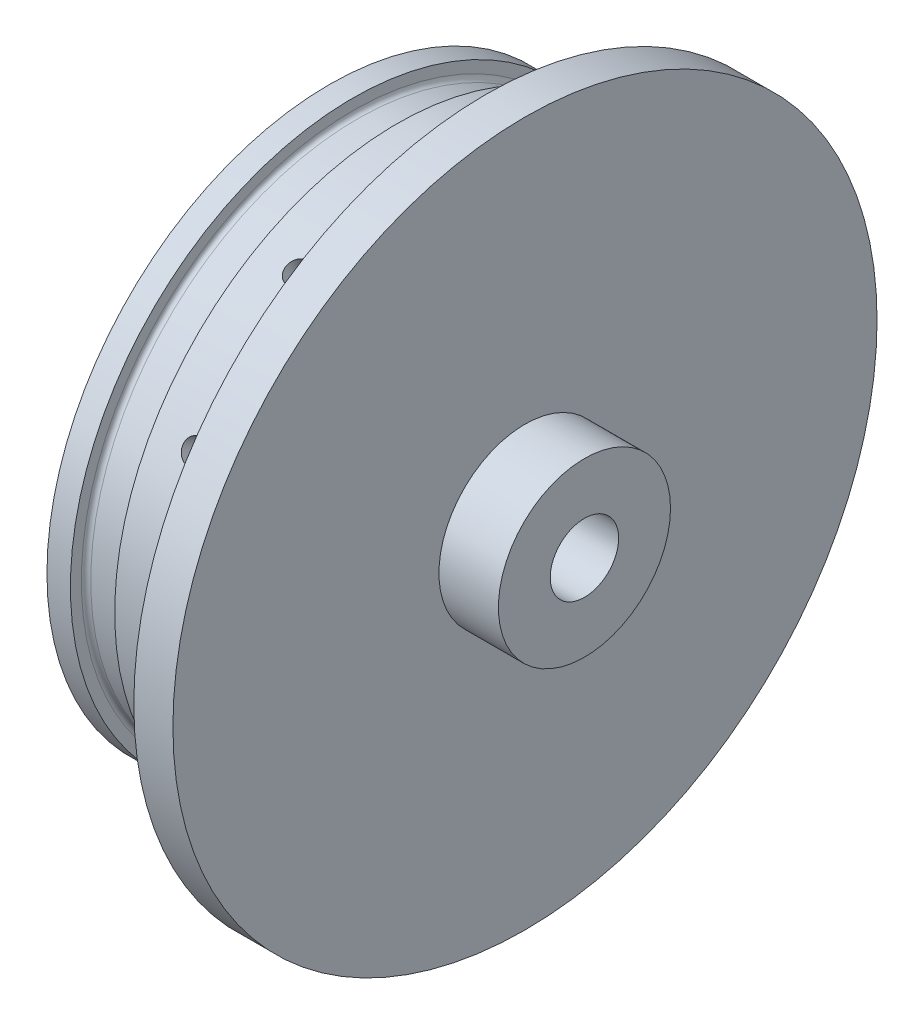
SolidWorks part; units mm, degrees
material "7075-T6 (SN)"
ref_plane "Front Plane" through (0, 0, 0) normal (0, 0, 1) x (1, 0, 0)
ref_plane "Top Plane" through (0, 0, 0) normal (0, 1, 0) x (1, 0, 0)
ref_plane "Right Plane" through (0, 0, 0) normal (1, 0, 0) x (0, 0, -1)
sketch "Sketch1" plane through (0, 0, 0) normal (1, 0, 0) x (0, 0, -1)
  circle A0 centre (0, 0) radius 57.15
  dimension "D1" = 114.3
extrude "Boss-Extrude1" add sketch "Sketch1" along normal blind 6.35
sketch "Sketch2" plane through (0, 0, 0) normal (-1, 0, 0) x (0, 0, 1)
  circle A0 centre (0, 0) radius 45.847
  dimension "D1" = 91.694
extrude "Boss-Extrude2" add sketch "Sketch2" along normal blind 25.4
sketch "Sketch10" plane through (0, 0, 0) normal (0, 1, 0) x (1, 0, 0)
  line L0 (0, 0) -> (-53.2238, 0) construction
  line L1 (-26.2636, 0) -> (26.2636, 0) construction
  line L2 (0, 0) -> (0, 64.5447) construction
  line L3 (0, -62.865) -> (0, 62.865) construction
ref_plane "Plane1" through (0, 0, -45.847) normal (0, 0, -1) x (-1, 0, 0)
sketch "Sketch11" plane through (0, 0, -45.847) normal (0, 0, -1) x (-1, 0, 0)
  line L0 (0, 0) -> (53.2238, 0) construction
  line L1 (0, -45.847) -> (0, 45.847) construction
  circle A0 centre (7.62, 0) radius 1.8986
  dimension "D2" = 3.7973
  dimension "D1" = 7.62
extrude "Cut-Extrude3" cut sketch "Sketch11" against normal blind 10.16
pattern_circular "CirPattern1" count 12 over 360 about axis through (0, 0, 0) along (-1, 0, 0) of "Cut-Extrude3" reverse direction yes
sketch "Sketch15" plane through (6.35, 0, 0) normal (1, 0, 0) x (0, 0, -1)
  circle A0 centre (0, 0) radius 5.5562
  dimension "D1" = 11.1125
extrude "Cut-Extrude4" cut sketch "Sketch15" against normal through all both and the other way through all
sketch "Sketch16" plane through (0, 0, 0) normal (0, 0, 1) x (1, 0, 0)
  line L0 (-9.5186, 45.847) -> (-25.4, 45.847) construction
  line L1 (-21.59, 45.847) -> (-14.4018, 45.847)
  line L2 (-21.59, 45.847) -> (-21.59, 44.069)
  line L3 (-20.828, 43.307) -> (-15.1638, 43.307)
  line L4 (-14.4018, 45.847) -> (-14.4018, 44.069)
  line L5 (0, 0) -> (-53.2238, 0) construction
  line L6 (-25.4, 45.847) -> (-25.4, -45.847) construction
  arc A0 (-14.4018, 44.069) -> (-15.1638, 43.307) centre (-15.1638, 44.069) cw
  arc A1 (-20.828, 43.307) -> (-21.59, 44.069) centre (-20.828, 44.069) cw
  point P8 (-26.6119, 0)
  point P13 (-14.4018, 43.307)
  point P16 (-21.59, 43.307)
  dimension "D4" = 0.762
  dimension "D1" = 43.307
  dimension "D2" = 3.81
  dimension "D3" = 7.1882
revolve "Cut-Revolve1" cut sketch "Sketch16" angle 360 about L0
sketch "Sketch17" plane through (6.35, 0, 0) normal (1, 0, 0) x (0, 0, -1)
  circle A0 centre (0, 0) radius 13.97
  circle A1 centre (0, 0) radius 5.5562
  dimension "D1" = 27.94
  dimension "D2" = 11.1125
extrude "Boss-Extrude3" add sketch "Sketch17" along normal blind 9.652
cosmetic thread "Cosmetic Thread1" parameters "D2"=23.1953
sketch "Sketch18" plane through (-25.4, 0, 0) normal (-1, 0, 0) x (0, 0, 1)
  circle A0 centre (0, 0) radius 38.354
  dimension "D1" = 76.708
extrude "Cut-Extrude5" cut sketch "Sketch18" against normal blind 6.604
sketch "Sketch19" plane through (-18.796, 0, 0) normal (-1, 0, 0) x (0, 0, 1)
  line L0 (0, 0) -> (0, 57.15) construction
  circle A0 centre (0, 0) radius 57.15 construction
  circle A1 centre (0, 33.3375) radius 1.1303
  circle A2 centre (23.5732, 23.5732) radius 1.1303
  circle A3 centre (33.3375, 0) radius 1.1303
  circle A4 centre (23.5732, -23.5732) radius 1.1303
  circle A5 centre (0, -33.3375) radius 1.1303
  circle A6 centre (-23.5732, -23.5732) radius 1.1303
  circle A7 centre (-33.3375, 0) radius 1.1303
  circle A8 centre (-23.5732, 23.5732) radius 1.1303
  point P24 (0, 0)
  dimension "D2" = 2.2606
  dimension "D1" = 33.3375
  dimension "D3" = 8
extrude "Cut-Extrude6" cut sketch "Sketch19" against normal blind 6.35
sketch "Sketch20" plane through (0, 0, 0) normal (0, 0, 1) x (1, 0, 0)
  line L0 (0, 0) -> (-18.796, 0)
  line L1 (-18.796, 25.4) -> (0, 12.7)
  line L3 (-18.796, 25.4) -> (-18.796, 0)
  line L4 (0, 45.847) -> (0, -45.847) construction
  line L5 (0, 12.7) -> (0, 0)
  dimension "D1" = 25.4
  dimension "D2" = 18.796
  dimension "D3" = 12.7
revolve "Cut-Revolve2" cut sketch "Sketch20" angle 360 about L0
